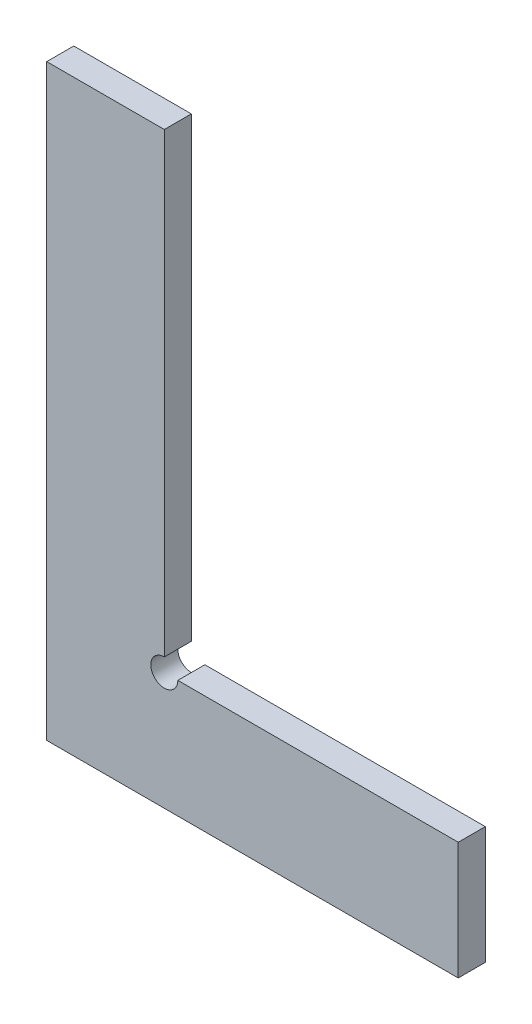
SolidWorks part; units mm, degrees
material "2219-O"
ref_plane "Front Plane" through (0, 0, 0) normal (0, 0, 1) x (1, 0, 0)
ref_plane "Top Plane" through (0, 0, 0) normal (0, 1, 0) x (1, 0, 0)
ref_plane "Right Plane" through (0, 0, 0) normal (1, 0, 0) x (0, 0, -1)
sketch "Çizim1" plane through (0, 0, 0) normal (0, 0, 1) x (1, 0, 0)
  line L0 (0, 0) -> (0, 100)
  line L1 (0, 100) -> (20, 100)
  line L2 (0, 0) -> (70, 0)
  line L3 (70, 0) -> (70, 20)
  line L4 (70, 20) -> (22.3, 20)
  line L5 (20, 22.3) -> (20, 100)
  arc A0 (20, 22.3) -> (22.3, 20) centre (20, 20) ccw
  dimension "D5" = 4.6
  dimension "D1" = 100
  dimension "D2" = 20
  dimension "D3" = 70
  dimension "D4" = 20
extrude "Yükseklik-Ekstrüzyon1" add sketch "Çizim1" along normal blind 4.6
sketch "Çizim3" plane through (0, 0, 0) normal (0, -1, 0) x (1, 0, 0)
  circle A0 centre (11.5, 2.3) radius 1.5
  circle A1 centre (58.5, 2.3) radius 1.5
extrude "Kes-Ekstrüzyon1" cut sketch "Çizim3" against normal blind 4.4
thread "Diş1" pitch 0.6 method cut profile "Thread Profile1" start angle 0, offset 0, length 4.4, pitch 0.6, diameter 3
ref_plane "Düzlem1" through (13, 0, 2.3) normal (0, 0, 1) x (1, 0, 0)
sketch "Thread Profile1" plane through (13, 0, 2.3) normal (0, 0, 1) x (1, 0, 0)
  line L0 (0, 0) -> (0, 0.6) construction
  line L1 (0, 0) -> (0.3248, 0.1875)
  line L2 (0.3248, 0.1875) -> (0.3248, 0.2625)
  line L3 (0.3248, 0.2625) -> (0, 0.45)
  line L4 (0.3248, 0.225) -> (0, 0.225) construction
  line L11 (0, 0) -> (0, 0.45)
  point P2 (0, 0)
  dimension "Pitch" = 0.6
  dimension "Profile_Angle" = 60
  dimension "Profile_Land" = 0.075
  dimension "Profile_Height" = 0.3248
thread "Diş2" pitch 0.6 method cut profile "Thread Profile2" start angle 0, offset 0, length 4.4, pitch 0.6, diameter 3
ref_plane "Düzlem2" through (60, 0, 2.3) normal (0, 0, 1) x (1, 0, 0)
sketch "Thread Profile2" plane through (60, 0, 2.3) normal (0, 0, 1) x (1, 0, 0)
  line L0 (0, 0) -> (0, 0.6) construction
  line L1 (0, 0) -> (0.3248, 0.1875)
  line L2 (0.3248, 0.1875) -> (0.3248, 0.2625)
  line L3 (0.3248, 0.2625) -> (0, 0.45)
  line L4 (0.3248, 0.225) -> (0, 0.225) construction
  line L11 (0, 0) -> (0, 0.45)
  point P2 (0, 0)
  dimension "Pitch" = 0.6
  dimension "Profile_Angle" = 60
  dimension "Profile_Land" = 0.075
  dimension "Profile_Height" = 0.3248
